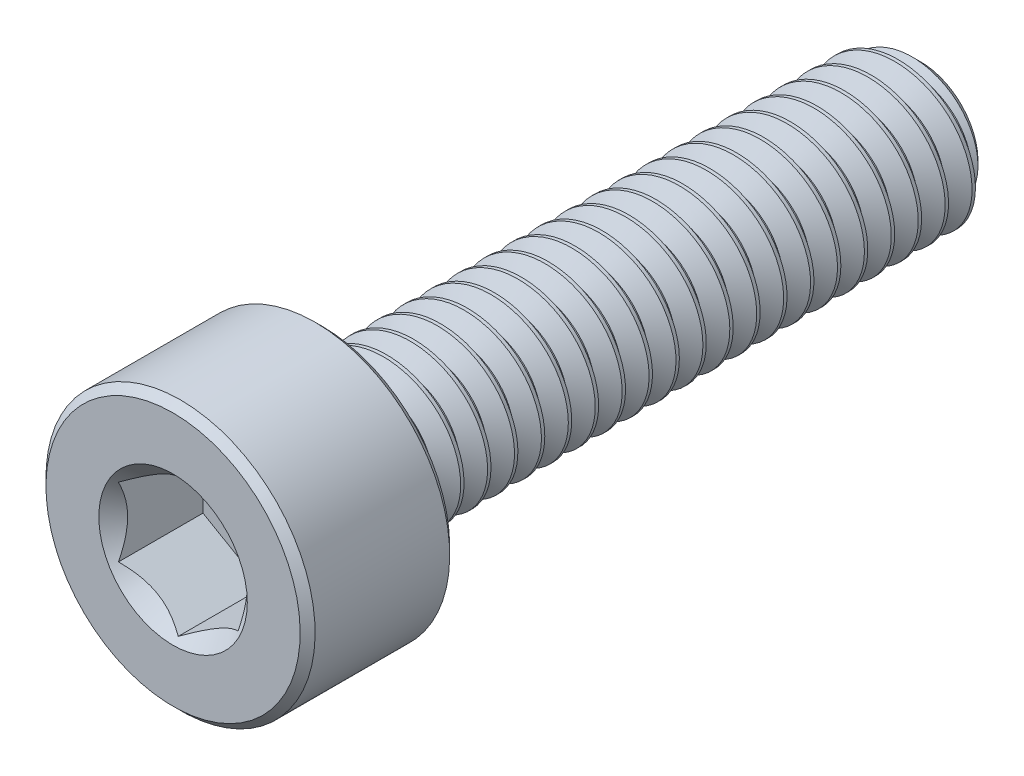
SolidWorks part; units mm, degrees
ref_plane "Front Plane" through (0, 0, 0) normal (0, 0, 1) x (1, 0, 0)
ref_plane "Top Plane" through (0, 0, 0) normal (0, 1, 0) x (1, 0, 0)
ref_plane "Right Plane" through (0, 0, 0) normal (1, 0, 0) x (0, 0, -1)
sketch "Sketch1" plane through (0, 0, 0) normal (1, 0, 0) x (0, 0, -1)
  line L0 (-6.25, 0) -> (6.25, 0) construction
  line L1 (6.25, 0) -> (6.25, 0.9577) construction
  line L2 (6.25, 0.9577) -> (5.9577, 1.25) construction
  line L3 (5.9577, 1.25) -> (5.9125, 1.25) construction
  line L4 (5.9125, 1.25) -> (-3.75, 1.25) construction
  line L5 (-3.75, 1.25) -> (-3.75, 2.25) construction
  line L6 (-3.75, 2.25) -> (-6.25, 2.25) construction
  line L7 (-6.25, 2.25) -> (-6.25, 0) construction
  line L8 (6.25, 0.9577) -> (6.25, 1.25) construction
  line L9 (6.2219, 1.2987) -> (6.4469, 0.909) construction
  line L10 (6.4469, 0.909) -> (6.6719, 1.2987) construction
  line L11 (6.6719, 1.2987) -> (6.2219, 1.2987) construction
  line L12 (6.4469, 1.2987) -> (6.4469, 1.25) construction
  line L13 (6.4469, 0.909) -> (6.4469, 0.9577) construction
  line L14 (6.4187, 0.9577) -> (6.475, 0.9577) construction
  line L15 (6.25, 1.25) -> (6.6437, 1.25) construction
  line L16 (6.2359, 1.2744) -> (6.6578, 1.2744) construction
  line L17 (6.25, 0) -> (6.25, -1.25) construction
  line L18 (-3.875, 2.25) -> (-3.75, 2.125) construction
  line L19 (-6.125, 2.25) -> (-6.25, 2.125) construction
  line L20 (-3.75, 1.25) -> (-3.75, 0) construction
  line L21 (-3.75, 0.625) -> (-0.4167, 0.625) construction
  line L22 (-0.4167, 0.625) -> (2.9167, 0.625) construction
  line L23 (2.9167, 0.625) -> (6.25, 0.625) construction
  line L24 (-0.4167, 0.625) -> (-0.4167, 1.25) construction
  line L25 (-0.4167, 1.25) -> (-0.4167, 2.25) construction
  line L26 (2.9167, 0.625) -> (2.9167, 2.25) construction
  point P0 (-6.25, 1)
  point P3 (5.125, 1.25)
  point P4 (0, 0)
  point P18 (2.9167, 1.25)
  point P22 (6.4469, 0.9577)
  point P24 (5.9125, 1.25)
  point P25 (6.4469, 1.25)
  point P28 (6.4469, 1.2744)
  point P29 (5.125, -1.25)
  point P30 (-0.4167, 1.25)
  point P31 (-5, 2.25)
  point P37 (-4.1875, 2.25)
  point P38 (-6.0625, 2.25)
  point P45 (-0.4167, 0.625)
  point P46 (2.9167, 0.625)
  dimension "D2" = 0.0563
  dimension "D7" = 0.125
  dimension "D8" = 0.125
  dimension "D9" = 0.125
  dimension "D10" = 0.0625
  dimension "D11" = 0.3125
  dimension "Drive Size" = 2
  dimension "Head Diameter" = 4.5
  dimension "Head Height" = 2.5
  dimension "Thread Pitch" = 0.45
  dimension "Thread Size" = 2.5
  dimension "Length" = 10
  dimension "D12" = 0.3375
  dimension "D4" = 1.125
  dimension "D3" = 45
sketch "Sketch2" plane through (0, 0, 0) normal (1, 0, 0) x (0, 0, -1)
  line L0 (-6.25, 0) -> (-6.25, 2.125)
  line L1 (-6.125, 2.25) -> (-3.875, 2.25)
  line L2 (-3.75, 2.125) -> (-3.75, 1.375)
  line L4 (5.9577, 1.25) -> (6.25, 0.9577)
  line L5 (6.25, 0.9577) -> (6.25, 0)
  line L6 (-3.75, 2.25) -> (-6.25, 2.25) construction
  line L7 (6.25, 0) -> (-6.25, 0)
  line L8 (-6.125, 2.25) -> (-6.25, 2.125) construction
  line L10 (-6.125, 2.25) -> (-6.25, 2.125)
  line L14 (-3.875, 2.25) -> (-3.75, 2.125) construction
  line L16 (-3.875, 2.25) -> (-3.75, 2.125)
  line L17 (-3.75, 1.25) -> (-3.75, 2.25) construction
  line L19 (-3.625, 1.25) -> (5.9577, 1.25)
  line L20 (5.9125, 1.25) -> (-3.75, 1.25) construction
  arc A1 (-3.75, 1.375) -> (-3.625, 1.25) centre (-3.625, 1.375) ccw
  dimension "D3" = 0.125
revolve "Revolve1" add sketch "Sketch2" angle 360 about L7
sketch "Sketch3" plane through (0, 0, 6.25) normal (0, 0, 1) x (1, 0, 0)
  line L1 (1, -0.5774) -> (1, 0.5774)
  line L2 (1, 0.5774) -> (0, 1.1547)
  line L3 (0, 1.1547) -> (-1, 0.5774)
  line L4 (-1, 0.5774) -> (-1, -0.5774)
  line L5 (-1, -0.5774) -> (0, -1.1547)
  line L6 (0, -1.1547) -> (1, -0.5774)
  circle A0 centre (0, 0) radius 1 construction
  circle A1 centre (0, 0) radius 2.25 construction
  circle A2 centre (0, 0) radius 2.25 construction
  circle A3 centre (0, 0) radius 1.1547 construction
  point P13 (0, 0)
  dimension "D1" = 2.3094
extrude "Cut-Extrude1" cut sketch "Sketch3" against normal offset from surface (1.5 mm away) 1 up to face at (0, 2.125, 3.75)
sketch "Sketch4" plane through (0, 0, 6.25) normal (0, 0, 1) x (1, 0, 0)
  circle A0 centre (0, 0) radius 1.2413
  dimension "D1" = 2.4826
extrude "Cut-Extrude2" cut sketch "Sketch4" against normal up to vertex (1.25 mm away) draft 45 up to point (0, 2.25, 5)
sketch "Sketch11" plane through (0, 0, 0) normal (1, 0, 0) x (0, 0, -1)
  line L0 (-6.25, 0) -> (6.25, 0) construction
  line L1 (-6.25, 0) -> (6.25, 0) construction
  line L2 (-1.875, 0) -> (-1.875, 1.25) construction
  line L3 (5.9125, 1.25) -> (-3.75, 1.25) construction
  line L4 (4.375, 0) -> (4.375, 1.25) construction
  line L6 (6.25, 0.9577) -> (6.25, 1.25) construction
  point P2 (-1.875, 0)
  point P3 (4.375, 0)
  dimension "D1" = 1.875
  dimension "D2" = 1.875
sketch "Sketch6" plane through (0, 0, -6.25) normal (0, 0, -1) x (-1, 0, 0)
  circle A0 centre (0, 0) radius 1.25
curve "Helix/Spiral1" pitch 0.45 height 10.45 turns 23.2222
sketch "Sketch10" plane through (0, 0, 0) normal (1, 0, 0) x (0, 0, -1)
  line L0 (-3.625, -2.25) -> (-3.625, 2.25)
  line L5 (-6.25, 0) -> (6.25, 0) construction
  line L6 (-3.625, 1.25) -> (-3.625, -1.25) construction
  point P3 (-3.625, 0)
split "Split1" trim tools "Sketch10" bodies to split 106 resulting bodies 114 115
sketch "Sketch7" plane through (0, 0, 0) normal (1, 0, 0) x (0, 0, -1)
  line L0 (6.2359, 1.2744) -> (6.6578, 1.2744)
  line L1 (6.6578, 1.2744) -> (6.475, 0.9577)
  line L2 (6.475, 0.9577) -> (6.4187, 0.9577)
  line L3 (6.4187, 0.9577) -> (6.2359, 1.2744)
sweep "Cut-Sweep1" cut profiles "Sketch7" path "Helix/Spiral1" align with end faces yes
sketch "Sketch8" plane through (0, 0, 0) normal (1, 0, 0) x (0, 0, -1)
  line L0 (-3.75, 0) -> (-3.75, 1.25)
  line L1 (-3.625, -1.25) -> (-3.625, 1.25) construction
  line L2 (-3.75, 1.25) -> (-3.625, 1.25)
  line L4 (-3.625, 1.25) -> (-2.9033, 0)
  line L5 (-2.9033, 0) -> (-3.75, 0)
  line L6 (5.9125, 1.25) -> (-3.75, 1.25) construction
  line L7 (-6.25, 0) -> (6.25, 0) construction
  dimension "D1" = 60
revolve "Revolve2" add sketch "Sketch8" angle 360 about L5
equation "\"D2@Sketch1\" = \"Thread Pitch@Sketch1\" / 8"
equation "\"D4@Helix/Spiral1\" = \"Thread Pitch@Sketch1\""
equation "\"D7@Sketch1\" = \"Head Height@Sketch1\" * .05"
equation "\"D8@Sketch1\"=\"D7@Sketch1\""
equation "\"D9@Sketch1\"=\"D7@Sketch1\""
equation "\"D10@Sketch1\"=\"D7@Sketch1\"/2"
equation "\"D11@Sketch1\"=\"D10@Sketch1\"*5"
equation "\"D4@Sketch1\"=\"Thread Pitch@Sketch1\"*2.5"
equation "\"D12@Sketch1\"=\"Thread Pitch@Sketch1\"*.75"
equation "\"D3@Helix/Spiral1\"=\"Length@Sketch1\"+\"Thread Pitch@Sketch1\""
equation "\"D3@Sketch2\"=\"Thread Size@Sketch1\"*0.05"
equation "\"D1@Sketch11\"=\"Length@Sketch1\"*0.1875"
equation "\"D2@Sketch11\"=\"D1@Sketch11\""
equation "\"D1@Sketch4\"=\"D1@Sketch3\"*1.075"
